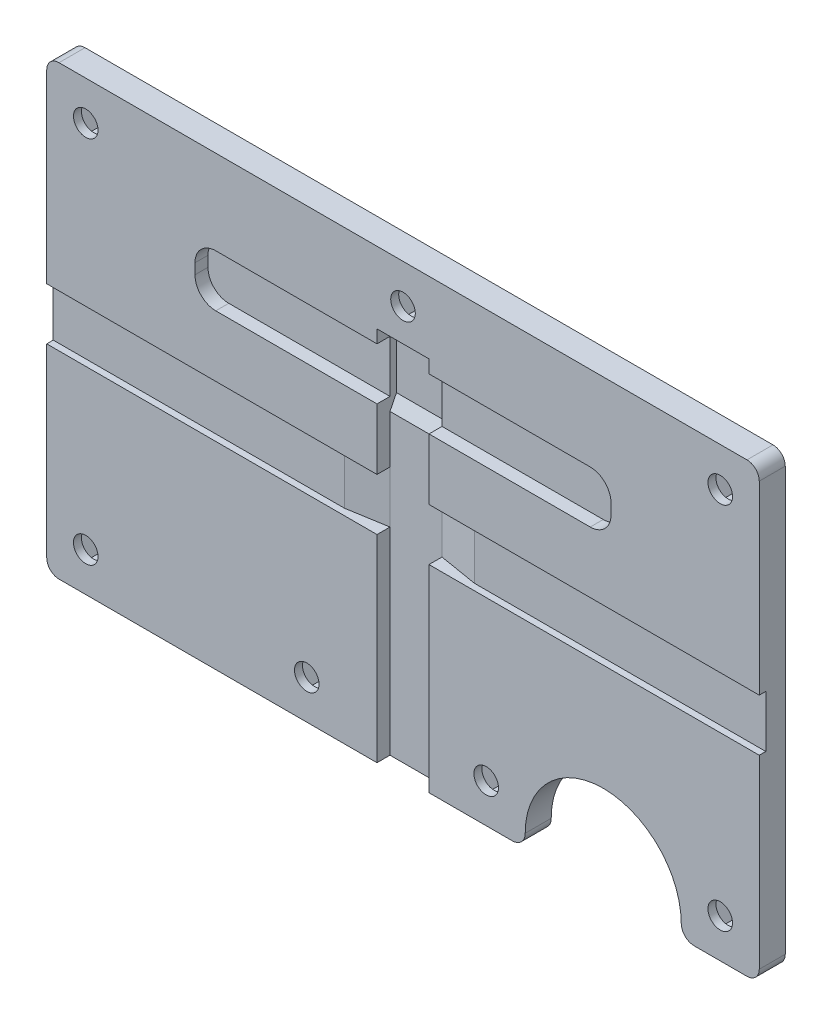
SolidWorks part; units mm, degrees
ref_plane "Front Plane" through (0, 0, 0) normal (0, 0, 1) x (1, 0, 0)
ref_plane "Top Plane" through (0, 0, 0) normal (0, 1, 0) x (1, 0, 0)
ref_plane "Right Plane" through (0, 0, 0) normal (1, 0, 0) x (0, 0, -1)
ref_plane "Plane1" through (0, 0, 1.6) normal (0, 0, 1) x (1, 0, 0)
sketch "Sketch1" plane through (0, 0, 1.6) normal (0, 0, 1) x (1, 0, 0)
  line L0 (-17.6412, 51.7305) -> (-17.6412, 0.1205)
  line L1 (-16.1412, -1.3795) -> (39.1913, -1.3795)
  line L2 (61.4163, -1.3795) -> (67.8538, -1.3795)
  line L3 (69.3538, 0.1205) -> (69.3538, 51.7305)
  line L4 (67.8538, 53.2305) -> (-16.1412, 53.2305)
  line L5 (25.8563, 53.1969) -> (25.8563, 50053.1969) construction
  line L6 (59.8288, 0.6891) -> (59.8288, -49999.3109) construction
  line L7 (-12.8787, 3.383) -> (36.0163, 3.383) construction
  circle A0 centre (-12.8787, 48.468) radius 1.5
  circle A1 centre (-12.8787, 3.383) radius 1.5
  circle A2 centre (64.5913, 3.383) radius 1.5
  circle A3 centre (64.5913, 48.468) radius 1.5
  circle A4 centre (14.1088, 3.383) radius 1.5
  circle A5 centre (36.0163, 3.383) radius 1.5
  circle A6 centre (25.8563, 48.468) radius 1.5
  arc A7 (-17.6412, 0.1205) -> (-16.1412, -1.3795) centre (-16.1412, 0.1205) ccw
  arc A8 (39.1913, -1.3795) -> (40.7788, 0.208) centre (39.1913, 0.208) ccw
  arc A9 (40.7788, 0.208) -> (59.8288, 0.208) centre (50.3038, 0.208) cw
  arc A10 (59.8288, 0.208) -> (61.4163, -1.3795) centre (61.4163, 0.208) ccw
  arc A11 (67.8538, -1.3795) -> (69.3538, 0.1205) centre (67.8538, 0.1205) ccw
  arc A12 (69.3538, 51.7305) -> (67.8538, 53.2305) centre (67.8538, 51.7305) ccw
  arc A13 (-16.1412, 53.2305) -> (-17.6412, 51.7305) centre (-16.1412, 51.7305) ccw
  point P35 (25.8563, 53.2305)
  point P36 (11.5688, 3.383)
  dimension "D1" = 4.7625
  dimension "D2" = 3
  dimension "D4" = 86.995
  dimension "D6" = 4.7625
  dimension "D13" = 1.5875
  dimension "D14" = 9.525
  dimension "D3" = 4.7625
  dimension "D5" = 54.61
  dimension "D7" = 4.7625
  dimension "D8" = 4.7625
  dimension "D9" = 4.7625
  dimension "D10" = 4.7625
  dimension "D11" = 4.7625
  dimension "D12" = 4.7625
  dimension "D15" = 19.05
  dimension "D16" = 4.7625
  dimension "D17" = 4.7625
  dimension "D18" = 3.175
  dimension "D19" = 31.75
extrude "Boss-Extrude1" add sketch "Sketch1" against normal blind 3.175
sketch "Sketch2" plane through (0, 0, 1.6) normal (0, 0, 1) x (1, 0, 0)
  line L0 (-17.6412, 51.7305) -> (-17.6412, 0.1205) construction
  line L1 (-17.6412, 29.1005) -> (69.3538, 29.1005)
  line L2 (-17.6412, 29.1005) -> (-17.6412, 22.7505)
  line L3 (-17.6412, 22.7505) -> (69.3538, 22.7505)
  line L4 (69.3538, 29.1005) -> (69.3538, 22.7505)
  line L5 (69.3538, 51.7305) -> (69.3538, 0.1205) construction
  point P10 (-17.6412, 25.9255)
  dimension "D1" = 6.35
extrude "Cut-Extrude1" cut sketch "Sketch2" against normal blind 0.7937
sketch "Sketch3" plane through (0, 0, 1.6) normal (0, 0, 1) x (1, 0, 0)
  line L0 (-16.1412, -1.3795) -> (67.8538, -1.3795) construction
  line L1 (22.6813, 29.1005) -> (29.0313, 29.1005)
  line L2 (22.6813, 29.1005) -> (22.6813, -1.3795)
  line L3 (22.6813, -1.3795) -> (29.0313, -1.3795)
  line L4 (29.0313, 29.1005) -> (29.0313, -1.3795)
  line L5 (69.3538, 29.1005) -> (-17.6412, 29.1005) construction
  point P8 (25.8563, -1.3795)
  dimension "D1" = 6.35
extrude "Cut-Extrude2" cut sketch "Sketch3" against normal blind 1.5875
chamfer "Chamfer1" distance 4.7625 distance2 0.7937 2 edges at (22.6813, 25.9255, 0.8063) (29.0313, 25.9255, 0.8063) first distance on face at (2.52, 25.9255, 0.8063) first distance on face at (49.1925, 25.9255, 0.8063)
sketch "Sketch4" plane through (0, 0, 1.6) normal (0, 0, 1) x (1, 0, 0)
  line L0 (29.0313, 29.1005) -> (22.6813, 29.1005) construction
  line L1 (22.6813, 44.4992) -> (29.0313, 44.4992)
  line L2 (22.6813, 44.4992) -> (22.6813, 29.1005)
  line L3 (22.6813, 29.1005) -> (29.0313, 29.1005)
  line L4 (29.0313, 44.4992) -> (29.0313, 29.1005)
  line L6 (25.8563, 44.4992) -> (25.8563, -49955.5008) construction
  circle A0 centre (25.8563, 48.468) radius 1.5 construction
  point P6 (25.8563, 29.1005)
  point P7 (25.8563, 29.1005)
  point P17 (25.8563, 44.4992)
  dimension "D1" = 3.9688
extrude "Cut-Extrude3" cut sketch "Sketch4" against normal blind 1.5875
sketch "Sketch6" plane through (0, 0, 0.0125) normal (0, 0, 1) x (1, 0, 0)
  line L0 (25.8563, 44.1805) -> (25.8563, -49955.8195) construction
  line L1 (22.6813, 42.9117) -> (29.0313, 42.9117)
  line L2 (22.6813, 42.9117) -> (22.6813, 36.5617)
  line L3 (22.6813, 36.5617) -> (29.0313, 36.5617)
  line L4 (29.0313, 42.9117) -> (29.0313, 36.5617)
  line L5 (29.0313, 44.4992) -> (22.6813, 44.4992) construction
  line L6 (29.0313, 29.1005) -> (29.0313, 44.4992) construction
  line L7 (29.0313, 44.4992) -> (22.6813, 44.4992) construction
  point P8 (25.8563, 44.4992)
  point P9 (25.8563, 42.9117)
  dimension "D1" = 1.5875
  dimension "D2" = 6.35
extrude "Cut-Extrude4" cut sketch "Sketch6" against normal blind 0.7937
chamfer "Chamfer2" distance 1.5875 distance2 0.7937 2 edges at (25.8563, 36.5617, 0.0125) (25.8563, 42.9117, 0.0125) first distance on face at (25.8563, 21.7583, 0.0125) first distance on face at (25.8563, 43.7055, 0.0125)
sketch "Sketch7" plane through (0, 0, 1.6) normal (0, 0, 1) x (1, 0, 0)
  line L0 (29.0313, 42.9117) -> (22.6813, 42.9117) construction
  line L1 (48.7163, 42.9117) -> (2.9963, 42.9117)
  line L2 (51.2563, 40.3717) -> (51.2563, 39.1017)
  line L3 (48.7163, 36.5617) -> (2.9963, 36.5617)
  line L4 (0.4563, 40.3717) -> (0.4563, 39.1017)
  line L7 (22.6813, 36.5617) -> (29.0313, 36.5617) construction
  arc A0 (51.2563, 40.3717) -> (48.7163, 42.9117) centre (48.7163, 40.3717) ccw
  arc A1 (48.7163, 36.5617) -> (51.2563, 39.1017) centre (48.7163, 39.1017) ccw
  arc A2 (0.4563, 39.1017) -> (2.9963, 36.5617) centre (2.9963, 39.1017) ccw
  arc A3 (0.4563, 40.3717) -> (2.9963, 42.9117) centre (2.9963, 40.3717) cw
  point P8 (25.8563, 42.9117)
  point P9 (25.8563, 42.9117)
  point P14 (51.2563, 36.5617)
  point P17 (0.4563, 36.5617)
  dimension "D2" = 2.54
  dimension "D1" = 50.8
extrude "Cut-Extrude5" cut sketch "Sketch7" against normal blind 1.5875
sketch "Sketch9" plane through (0, 0, -1.575) normal (0, 0, -1) x (-1, 0, 0)
  line L1 (-22.6231, 48.4534) -> (-24.2271, 51.2607)
  line L2 (-24.2271, 51.2607) -> (-27.4602, 51.2752)
  line L3 (-27.4602, 51.2752) -> (-29.0894, 48.4825)
  line L4 (-29.0894, 48.4825) -> (-27.4854, 45.6753)
  line L5 (-27.4854, 45.6753) -> (-24.2523, 45.6607)
  line L6 (-24.2523, 45.6607) -> (-22.6231, 48.4534)
  line L7 (-10.8756, 3.3755) -> (-12.4857, 6.1792)
  line L8 (-12.4857, 6.1792) -> (-15.7188, 6.1867)
  line L9 (-15.7188, 6.1867) -> (-17.3419, 3.3905)
  line L10 (-17.3419, 3.3905) -> (-15.7319, 0.5868)
  line L11 (-15.7319, 0.5868) -> (-12.4987, 0.5792)
  line L12 (-12.4987, 0.5792) -> (-10.8756, 3.3755)
  line L13 (16.1119, 3.3696) -> (14.5069, 6.1763)
  line L14 (14.5069, 6.1763) -> (11.2737, 6.1897)
  line L15 (11.2737, 6.1897) -> (9.6456, 3.3964)
  line L16 (9.6456, 3.3964) -> (11.2506, 0.5897)
  line L17 (11.2506, 0.5897) -> (14.4837, 0.5763)
  line L18 (14.4837, 0.5763) -> (16.1119, 3.3696)
  line L19 (16.1118, 48.4454) -> (14.5148, 51.2566)
  line L20 (14.5148, 51.2566) -> (11.2817, 51.2792)
  line L21 (11.2817, 51.2792) -> (9.6456, 48.4906)
  line L22 (9.6456, 48.4906) -> (11.2426, 45.6793)
  line L23 (11.2426, 45.6793) -> (14.4757, 45.6568)
  line L24 (14.4757, 45.6568) -> (16.1118, 48.4454)
  line L25 (-61.3581, 48.4682) -> (-62.9749, 51.2681)
  line L26 (-62.9749, 51.2681) -> (-66.208, 51.2679)
  line L27 (-66.208, 51.2679) -> (-67.8244, 48.4678)
  line L28 (-67.8244, 48.4678) -> (-66.2077, 45.6679)
  line L29 (-66.2077, 45.6679) -> (-62.9745, 45.6681)
  line L30 (-62.9745, 45.6681) -> (-61.3581, 48.4682)
  line L31 (-61.3581, 3.383) -> (-62.9747, 6.183)
  line L32 (-62.9747, 6.183) -> (-66.2079, 6.183)
  line L33 (-66.2079, 6.183) -> (-67.8244, 3.383)
  line L34 (-67.8244, 3.383) -> (-66.2079, 0.583)
  line L35 (-66.2079, 0.583) -> (-62.9747, 0.583)
  line L36 (-62.9747, 0.583) -> (-61.3581, 3.383)
  line L37 (-32.7843, 3.2953) -> (-34.3243, 6.1381)
  line L38 (-34.3243, 6.1381) -> (-37.5563, 6.2258)
  line L39 (-37.5563, 6.2258) -> (-39.2482, 3.4707)
  line L40 (-39.2482, 3.4707) -> (-37.7082, 0.6279)
  line L41 (-37.7082, 0.6279) -> (-34.4762, 0.5402)
  line L42 (-34.4762, 0.5402) -> (-32.7843, 3.2953)
  circle A0 centre (-25.8563, 48.468) radius 2.8 construction
  circle A1 centre (-14.1088, 3.383) radius 2.8 construction
  circle A2 centre (12.8787, 3.383) radius 2.8 construction
  circle A3 centre (12.8787, 48.468) radius 2.8 construction
  circle A4 centre (-64.5913, 48.468) radius 2.8 construction
  circle A5 centre (-64.5913, 48.468) radius 1.5 construction
  circle A6 centre (-25.8563, 48.468) radius 1.5 construction
  circle A7 centre (12.8787, 48.468) radius 1.5 construction
  circle A8 centre (12.8787, 3.383) radius 1.5 construction
  circle A9 centre (-14.1088, 3.383) radius 1.5 construction
  circle A10 centre (-64.5913, 3.383) radius 2.8 construction
  circle A11 centre (-36.0163, 3.383) radius 2.8 construction
  circle A12 centre (-36.0163, 3.383) radius 1.5 construction
  circle A13 centre (-64.5913, 3.383) radius 1.5 construction
  point P43 (0, 0)
  point P71 (0, 0)
  dimension "D1" = 5.6
extrude "Cut-Extrude6" cut sketch "Sketch9" against normal blind 2.2
